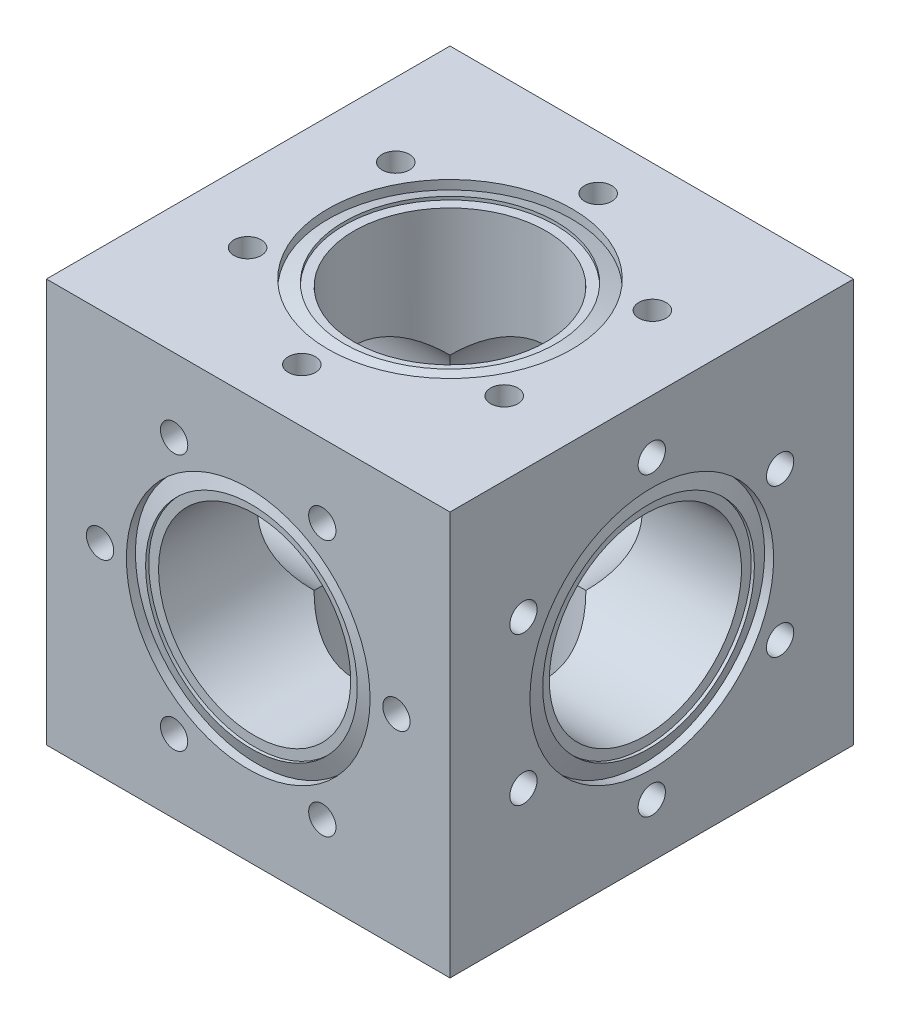
SolidWorks part; units mm, degrees
material "AISI 304"
ref_plane "Front Plane" through (0, 0, 0) normal (0, 0, 1) x (1, 0, 0)
ref_plane "Top Plane" through (0, 0, 0) normal (0, 1, 0) x (1, 0, 0)
ref_plane "Right Plane" through (0, 0, 0) normal (1, 0, 0) x (0, 0, -1)
sketch "Sketch1" plane through (0, 0, 0) normal (0, 0, 1) x (1, 0, 0)
  line L1 (40, -40) -> (-40, -40)
  line L2 (40, -40) -> (40, 40)
  line L3 (40, 40) -> (-40, 40)
  line L4 (-40, -40) -> (-40, 40)
  line L5 (40, -40) -> (-40, 40) construction
  line L6 (40, 40) -> (-40, -40) construction
  point P0 (0, 0)
  dimension "D1" = 40
extrude "Boss-Extrude1" add sketch "Sketch1" along normal mid plane 80
ref_axis "Axis1" through (-38.4175, 0, 0) along (1, 0, 0)
ref_axis "Axis2" through (0, 38.4175, 0) along (0, -1, 0)
ref_axis "Axis3" through (0, 0, 38.4175) along (0, 0, -1)
sketch "Sketch6" plane through (0, 0, 0) normal (0, 0, 1) x (1, 0, 0)
  line L0 (40, 24.1554) -> (38.2094, 24.1554)
  line L1 (40, -40) -> (40, 40) construction
  line L2 (38.2094, 24.1554) -> (39.365, 20.9804)
  line L3 (39.365, 20.9804) -> (38.73, 20.9804)
  line L4 (38.73, 20.9804) -> (38.73, 19.05)
  line L5 (-38.4175, 0) -> (38.4175, 0) construction
  line L6 (0, 0) -> (40, 0)
  line L7 (40, 0) -> (40, 24.1554)
  line L8 (40, 0) -> (68.0068, 0) construction
  line L9 (38.73, 19.05) -> (0, 19.05)
  line L10 (0, 38.4175) -> (0, -38.4175) construction
  line L11 (0, 19.05) -> (0, 0)
  dimension "D1" = 20
  dimension "D2" = 3.175
  dimension "D3" = 0.635
  dimension "D4" = 1.27
  dimension "D5" = 48.3108
  dimension "D6" = 38.1
revolve "Cut-Revolve1" cut sketch "Sketch6" angle 360 about L8
hole_wizard " Tapped Hole0" positions "Sketch4" profile "Sketch5" tap size "1/4-28" standard "ANSI Inch"
sketch "Sketch4" plane through (40, 0, 0) normal (1, 0, 0) x (0, 0, -1)
  circle A0 centre (0, 0) radius 29.3751 construction
  point P0 (0, 29.3751)
  dimension "D1" = 58.7502
sketch "Sketch5" plane through (40, 29.3751, 0) normal (0, 1, 0) x (0, 0, -1)
  line L0 (0, 0) -> (0, 11.7854)
  line L1 (0, 11.7854) -> (2.7051, 10.16)
  line L2 (2.7051, 10.16) -> (2.7051, 0)
  line L5 (2.7051, 0) -> (0, 0)
  line L10 (0, 11.7854) -> (-2.7051, 10.16) construction
  line L11 (0, -6.35) -> (0, 107.95) construction
  dimension "Tap Drill Dia." = 5.4102
  dimension "Tap Drill Depth" = 10.16
  dimension "Drill Angle" = 118
cosmetic thread "Hole Thread1" parameters "D1"=12.7, "D2"=6.35
hole_wizard " Tapped Hole1" positions "Sketch9" profile "Sketch8" tap size "1/4-28" standard "ANSI Inch"
sketch "Sketch9" plane through (0, 40, 0) normal (0, 1, 0) x (1, 0, 0)
  circle A0 centre (0, 0) radius 29.3751 construction
  point P0 (0, 29.3751)
  dimension "D1" = 58.7502
sketch "Sketch8" plane through (0, 40, -29.3751) normal (1, 0, 0) x (0, 0, 1)
  line L0 (0, 0) -> (0, 11.7854)
  line L1 (0, 11.7854) -> (2.7051, 10.16)
  line L2 (2.7051, 10.16) -> (2.7051, 0)
  line L5 (2.7051, 0) -> (0, 0)
  line L10 (0, 11.7854) -> (-2.7051, 10.16) construction
  line L11 (0, -6.35) -> (0, 107.95) construction
  dimension "Tap Drill Dia." = 5.4102
  dimension "Tap Drill Depth" = 10.16
  dimension "Drill Angle" = 118
cosmetic thread "Hole Thread2" parameters "D1"=12.7, "D2"=6.35
hole_wizard " Tapped Hole2" positions "Sketch11" profile "Sketch10" tap size "1/4-28" standard "ANSI Inch"
sketch "Sketch11" plane through (0, 0, 40) normal (0, 0, 1) x (1, 0, 0)
  circle A0 centre (0, 0) radius 29.3751 construction
  point P0 (29.3751, 0)
  dimension "D1" = 58.7502
sketch "Sketch10" plane through (29.3751, 0, 40) normal (1, 0, 0) x (0, -1, 0)
  line L0 (0, 0) -> (0, 11.7854)
  line L1 (0, 11.7854) -> (2.7051, 10.16)
  line L2 (2.7051, 10.16) -> (2.7051, 0)
  line L5 (2.7051, 0) -> (0, 0)
  line L10 (0, 11.7854) -> (-2.7051, 10.16) construction
  line L11 (0, -6.35) -> (0, 107.95) construction
  dimension "Tap Drill Dia." = 5.4102
  dimension "Tap Drill Depth" = 10.16
  dimension "Drill Angle" = 118
cosmetic thread "Hole Thread3" parameters "D1"=12.7, "D2"=6.35
pattern_circular "CirPattern1" count 6 over 360 about axis through (-38.4175, 0, 0) along (1, 0, 0) of " Tapped Hole0"
pattern_circular "CirPattern2" count 6 over 360 about axis through (0, 38.4175, 0) along (0, -1, 0) of " Tapped Hole1"
pattern_circular "CirPattern3" count 6 over 360 about axis through (0, 0, 38.4175) along (0, 0, -1) of " Tapped Hole2"
pattern_circular "CirPattern4" count 4 over 360 about axis through (0, 38.4175, 0) along (0, -1, 0) of "Cut-Revolve1"
pattern_circular "CirPattern5" count 4 over 360 about axis through (0, 0, 38.4175) along (0, 0, -1) skipping 2 of "Cut-Revolve1"
mirror "Mirror1" about plane through (0, 0, 0) normal (0, 0, 1) of "CirPattern3"
mirror "Mirror2" about plane through (0, 0, 0) normal (0, 1, 0) of "CirPattern2"
mirror "Mirror3" about plane through (0, 0, 0) normal (1, 0, 0) of "CirPattern1"
equation "\"D1@Boss-Extrude1\"=\"D1@Sketch1\"*2"
equation "\"D1@Sketch9\"=\"D1@Sketch4\""
equation "\"D1@Sketch11\"=\"D1@Sketch4\""
